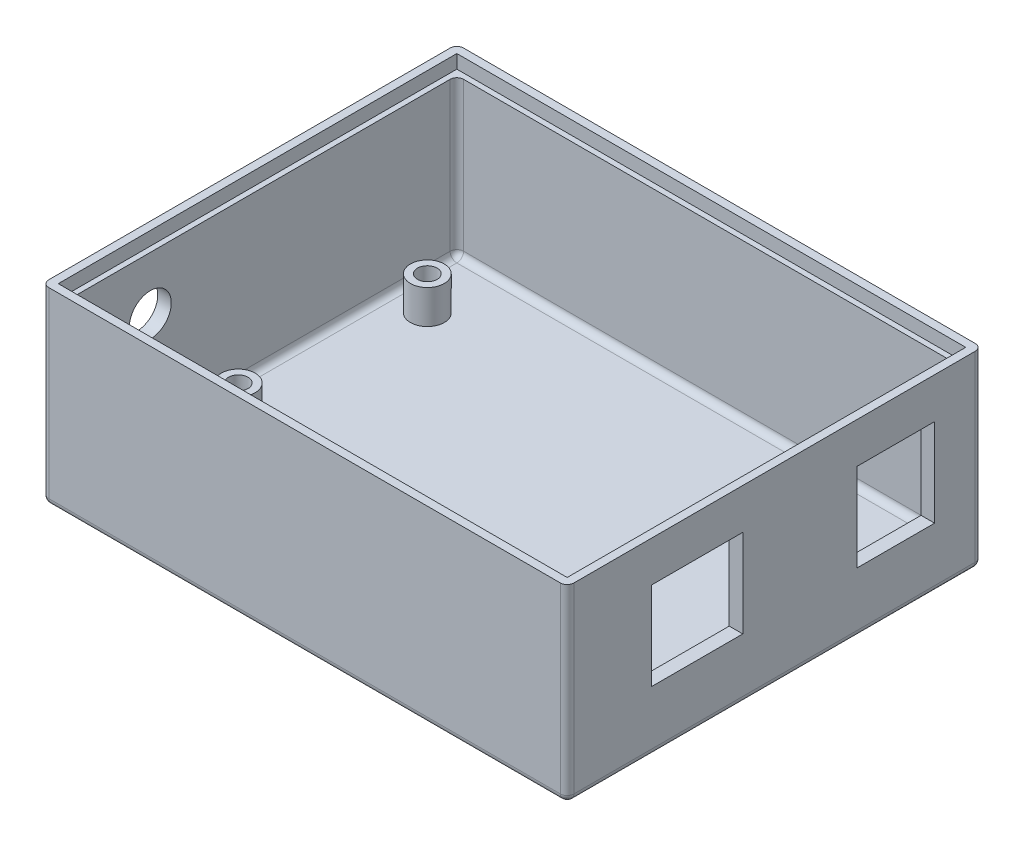
SolidWorks part; units mm, degrees
ref_plane "Front" through (0, 0, 0) normal (0, 0, 1) x (1, 0, 0)
ref_plane "Top" through (0, 0, 0) normal (0, 1, 0) x (1, 0, 0)
ref_plane "Right" through (0, 0, 0) normal (1, 0, 0) x (0, 0, -1)
sketch "Sketch1" plane through (0, 0, 0) normal (0, 1, 0) x (1, 0, 0)
  line L0 (35.8, -27.65) -> (-35.8, 27.65) construction
  line L1 (35.8, -27.65) -> (-35.8, -27.65) construction
  line L2 (35.8, -27.65) -> (35.8, 27.65) construction
  line L3 (35.8, 27.65) -> (-35.8, 27.65) construction
  line L4 (-35.8, -27.65) -> (-35.8, 27.65) construction
  line L5 (-35.8, 27.65) -> (-35.8, -27.65) construction
  line L6 (-35.8, -27.65) -> (35.8, 27.65) construction
  circle A0 centre (-32.6, 19.09) radius 2.5
  circle A1 centre (-32.6, -8.85) radius 2.5
  circle A2 centre (19.8, 24.15) radius 2.5
  circle A3 centre (18.5, -24.05) radius 2.5
  point P8 (0, 0)
  dimension "D5" = 5
  dimension "D6" = 5
  dimension "D7" = 5
  dimension "D8" = 5
  dimension "D3" = 51.1
  dimension "D13" = 27.94
  dimension "D2" = 71.6
  dimension "D9" = 55.3
  dimension "D10" = 17.3
  dimension "D14" = 3.5
  dimension "D4" = 8.56
  dimension "D12" = 48.2
  dimension "D11" = 16
extrude "Boss-Extrude1" add sketch "Sketch1" against normal blind 5
sketch "Sketch3" plane through (0, -5, 0) normal (0, -1, 0) x (1, 0, 0)
  line L0 (-39.8, -30.65) -> (37.8, 30.65) construction
  line L1 (-39.8, 30.65) -> (37.8, 30.65)
  line L2 (-39.8, 30.65) -> (-39.8, -30.65)
  line L3 (-39.8, -30.65) -> (37.8, -30.65)
  line L4 (37.8, 30.65) -> (37.8, -30.65)
  line L5 (-39.8, 30.65) -> (37.8, -30.65) construction
  line L6 (35.8, 27.65) -> (-35.8, -27.65) construction
  line L7 (35.8, 27.65) -> (-35.8, 27.65) construction
  line L8 (35.8, 27.65) -> (35.8, -27.65) construction
  line L9 (35.8, -27.65) -> (-35.8, -27.65) construction
  line L10 (-35.8, 27.65) -> (-35.8, -27.65) construction
  line L11 (-35.8, -27.65) -> (-35.8, 27.65) construction
  line L12 (-35.8, 27.65) -> (35.8, -27.65) construction
  point P0 (0, 0)
  point P5 (-1, 0)
  dimension "D3" = 71.6
  dimension "D4" = 55.3
  dimension "D1" = 77.6
  dimension "D2" = 61.3
  dimension "D5" = 1
extrude "Boss-Extrude2" add sketch "Sketch3" along normal blind 3
sketch "Sketch4" plane through (0, -5, 0) normal (0, 1, 0) x (1, 0, 0)
  line L0 (-39.8, -30.65) -> (-39.8, 30.65) construction
  line L1 (-39.8, -30.65) -> (37.8, -30.65)
  line L2 (-39.8, -30.65) -> (-39.8, 30.65)
  line L3 (-39.8, 30.65) -> (37.8, 30.65)
  line L4 (37.8, -30.65) -> (37.8, 30.65)
  line L5 (-37.8, -28.65) -> (35.8, -28.65)
  line L6 (-37.8, -28.65) -> (-37.8, 28.65)
  line L7 (-37.8, 28.65) -> (35.8, 28.65)
  line L8 (35.8, -28.65) -> (35.8, 28.65)
  line L9 (37.8, -30.65) -> (-39.8, -30.65) construction
  dimension "D1" = 2
  dimension "D2" = 2
  dimension "D3" = 2
  dimension "D4" = 2
extrude "Boss-Extrude3" add sketch "Sketch4" along normal blind 25
sketch "Sketch5" plane through (37.8, 0, 0) normal (1, 0, 0) x (0, 0, -1)
  line L2 (-18.2, 14) -> (-18.2, 1)
  line L3 (-18.2, 1) -> (-4.7, 1)
  line L4 (-4.7, 14) -> (-4.7, 1)
  line L6 (-24.05, -5) -> (-24.05, 0) construction
  line L7 (24.15, -5) -> (24.15, 0) construction
  line L9 (12.15, 14) -> (12.15, 1)
  line L10 (12.15, 1) -> (23.65, 1)
  line L11 (23.65, 14) -> (23.65, 1)
  line L13 (-21.55, 0) -> (-26.55, 0) construction
  line L15 (-18.2, 14) -> (-4.7, 14)
  line L16 (12.15, 14) -> (23.65, 14)
  dimension "D1" = 13
  dimension "D2" = 13.5
  dimension "D3" = 1
  dimension "D4" = 5.85
  dimension "D5" = 11.5
  dimension "D7" = 0.5
extrude "Cut-Extrude2" cut sketch "Sketch5" against normal up to next
fillet "Fillet1" radius 1 8 edges at (35.8, 7.5, -28.65) (-1, -5, -28.65) (35.8, 7.5, 28.65) (-1, -5, 28.65) (-37.8, 7.5, 28.65) (-37.8, 7.5, -28.65) (-37.8, -5, 0) (37.8, -8, 0)
fillet "Fillet2" [suppressed] radius 1
sketch "Sketch7" plane through (0, 20, 0) normal (0, 1, 0) x (1, 0, 0)
  line L0 (-39.8, -30.65) -> (37.8, -30.65) construction
  line L1 (-38.6, -29.45) -> (36.6, -29.45)
  line L2 (-38.6, -29.45) -> (-38.6, 29.45)
  line L3 (-38.6, 29.45) -> (36.6, 29.45)
  line L4 (36.6, -29.45) -> (36.6, 29.45)
  line L5 (-39.8, 30.65) -> (-39.8, -30.65) construction
  line L6 (37.8, 30.65) -> (-39.8, 30.65) construction
  line L7 (37.8, -30.65) -> (37.8, 30.65) construction
  point P12 (37.8, 0)
  dimension "D1" = 1.2
  dimension "D2" = 1.2
  dimension "D3" = 1.2
  dimension "D4" = 1.2
extrude "Cut-Extrude3" cut sketch "Sketch7" against normal blind 2
sketch "Sketch2" plane through (0, 0, 0) normal (0, 1, 0) x (1, 0, 0)
  circle A0 centre (-32.6, -8.85) radius 1
  circle A1 centre (-32.6, 19.09) radius 1
  circle A2 centre (19.8, 24.15) radius 1
  circle A3 centre (18.5, -24.05) radius 1
  circle A4 centre (-32.6, -8.85) radius 2.5 construction
  circle A5 centre (-32.6, 19.09) radius 2.5 construction
  circle A6 centre (19.8, 24.15) radius 2.5 construction
  circle A7 centre (18.5, -24.05) radius 2.5 construction
  dimension "D1" = 2
  dimension "D2" = 2
  dimension "D3" = 2
  dimension "D4" = 2
extrude "Cut-Extrude1" cut sketch "Sketch2" against normal through all
hole_wizard "CSK for M2.5 Flat Head Machine Screw1" positions "Sketch10" profile "Sketch11" countersink size "M2.5" standard "ANSI Metric" end condition through all
sketch "Sketch10" plane through (0, -8, 0) normal (0, -1, 0) x (-1, 0, 0)
  point P0 (32.6, 19.09)
  point P3 (32.6, -8.85)
  point P6 (-18.5, -24.05)
  point P9 (-19.8, 24.15)
sketch "Sketch11" plane through (-32.6, -8, -19.09) normal (1, 0, 0) x (0, 0, -1)
  line L0 (0, 0) -> (0, 28)
  line L1 (0, 28) -> (1.45, 28)
  line L2 (1.45, 28) -> (1.45, 1.3)
  line L3 (1.45, 1.3) -> (2.75, 0)
  line L5 (2.75, 0) -> (0, 0)
  line L6 (-1.45, 1.3) -> (-2.75, 0) construction
  line L11 (0, -6.35) -> (0, 107.95) construction
  dimension "Thru Hole Dia." = 2.9
  dimension "Thru Hole Depth" = 28
  dimension "Near C'Sink Dia." = 5.5
  dimension "Near C'Sink Angle" = 90
sketch "Sketch12" plane through (-39.8, 0, 0) normal (-1, 0, 0) x (0, 0, 1)
  line L5 (16.65, -8) -> (16.65, 10) construction
  line L6 (30.65, -8) -> (-30.65, -8) construction
  circle A0 centre (16.65, 10) radius 3.1
  dimension "D2" = 6.2
  dimension "D1" = 18
extrude "Cut-Extrude4" cut sketch "Sketch12" against normal blind 2
fillet "Fillet3" radius 1 8 edges at (-1.5, -8, -30.65) (37.5071, -7.7071, -30.65) (-1.5, -8, 30.65) (37.5071, -7.7071, 30.65) (-39.8, 6, 30.65) (-39.8, 6, -30.65) (37.8, 6.5, -30.65) (37.8, 6.5, 30.65)
fillet "Fillet4" radius 1 3 edges at (-39.5071, -7.7071, 30.3571) (-39.5071, -7.7071, -30.3571) (-39.8, -8, 0)
equation "\"D6@Sketch1\"=\"D5@Sketch1\""
equation "\"D7@Sketch1\"=\"D5@Sketch1\""
equation "\"D8@Sketch1\"=\"D5@Sketch1\""
equation "\"D2@Sketch2\"=\"D1@Sketch2\""
equation "\"D3@Sketch2\"=\"D1@Sketch2\""
equation "\"D4@Sketch2\"=\"D1@Sketch2\""
equation "\"D2@Sketch4\"=\"D1@Sketch4\""
equation "\"D3@Sketch4\"=\"D1@Sketch4\""
equation "\"D4@Sketch4\"=\"D1@Sketch4\""
equation "\"D1@Sketch3\"=\"D3@Sketch3\"+6"
equation "\"D2@Sketch3\"=\"D4@Sketch3\"+6"
equation "\"D3@Sketch7\"=\"D1@Sketch7\""
equation "\"D2@Sketch7\"=\"D1@Sketch7\""
equation "\"D4@Sketch7\"=\"D1@Sketch7\""
